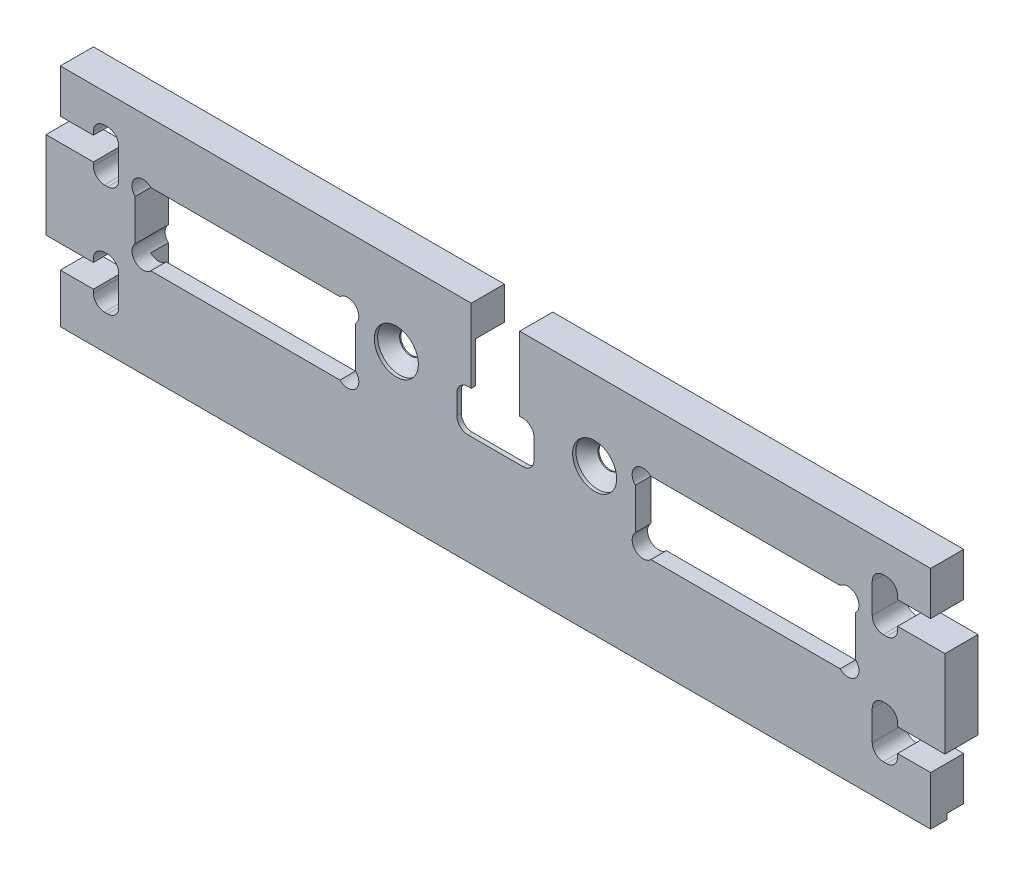
SolidWorks part; units mm, degrees
ref_plane "Front Plane" through (0, 0, 0) normal (0, 0, 1) x (1, 0, 0)
ref_plane "Top Plane" through (0, 0, 0) normal (0, 1, 0) x (1, 0, 0)
ref_plane "Right Plane" through (0, 0, 0) normal (1, 0, 0) x (0, 0, -1)
sketch "Sketch1" plane through (0, 0, 0) normal (0, 0, 1) x (1, 0, 0)
  line L0 (-39.5, 0) -> (39.5, 0) construction
  line L1 (-39.5, 10) -> (39.5, 10)
  line L2 (-39.5, 10) -> (-39.5, -10)
  line L3 (-39.5, -10) -> (39.5, -10)
  line L4 (39.5, 10) -> (39.5, -10)
  line L5 (-39.5, 10) -> (39.5, -10) construction
  line L6 (-39.5, -10) -> (39.5, 10) construction
  line L7 (0, 10) -> (0, -10) construction
  line L9 (-40.8, -3.95) -> (-39.5, -3.95)
  line L10 (-40.8, -3.95) -> (-40.8, 3.95)
  line L11 (-40.8, 3.95) -> (-39.5, 3.95)
  line L12 (-39.5, -3.95) -> (-39.5, 3.95)
  line L13 (-40.8, -3.95) -> (-39.5, 3.95) construction
  line L14 (-40.8, 3.95) -> (-39.5, -3.95) construction
  line L16 (40.8, 3.95) -> (39.5, 3.95)
  line L17 (40.8, -3.95) -> (40.8, 3.95)
  line L18 (40.8, -3.95) -> (39.5, -3.95)
  line L19 (-39.5, 5) -> (39.5, 5) construction
  line L20 (-35.35, 7.35) -> (-35.35, 2.65) construction
  line L21 (-36.5, 3.95) -> (-39.5, 3.95)
  line L22 (-36.5, 3.95) -> (-36.5, 6.05)
  line L23 (-36.5, 6.05) -> (-39.5, 6.05)
  line L24 (-39.5, 3.95) -> (-39.5, 6.05)
  line L25 (-36.5, 3.95) -> (-39.5, 6.05) construction
  line L26 (-36.5, 6.05) -> (-39.5, 3.95) construction
  line L27 (-34.2, 7.35) -> (-36.5, 7.35)
  line L28 (-34.2, 7.35) -> (-34.2, 2.65)
  line L29 (-34.2, 2.65) -> (-36.5, 2.65)
  line L30 (-36.5, 7.35) -> (-36.5, 2.65)
  line L31 (-34.2, 7.35) -> (-36.5, 2.65) construction
  line L32 (-34.2, 2.65) -> (-36.5, 7.35) construction
  line L33 (-34.2, -7.35) -> (-36.5, -7.35)
  line L34 (-34.2, -7.35) -> (-34.2, -2.65)
  line L35 (-34.2, -2.65) -> (-36.5, -2.65)
  line L36 (-36.5, -7.35) -> (-36.5, -2.65)
  line L37 (-36.5, -3.95) -> (-39.5, -3.95)
  line L38 (-36.5, -6.05) -> (-39.5, -6.05)
  line L39 (36.5, 3.95) -> (39.5, 3.95)
  line L40 (36.5, 6.05) -> (39.5, 6.05)
  line L41 (36.5, 7.35) -> (36.5, 2.65)
  line L42 (34.2, 7.35) -> (36.5, 7.35)
  line L43 (34.2, 7.35) -> (34.2, 2.65)
  line L44 (34.2, 2.65) -> (36.5, 2.65)
  line L45 (34.2, -2.65) -> (36.5, -2.65)
  line L46 (34.2, -7.35) -> (34.2, -2.65)
  line L47 (34.2, -7.35) -> (36.5, -7.35)
  line L48 (36.5, -7.35) -> (36.5, -2.65)
  line L49 (36.5, -6.05) -> (39.5, -6.05)
  line L50 (36.5, -3.95) -> (39.5, -3.95)
  point P0 (0, 0)
  point P10 (-40.15, 0)
  point P15 (-38, 5)
  point P35 (-35.35, 5)
  dimension "D1" = 79
  dimension "D2" = 20
  dimension "D4" = 1.3
  dimension "D7" = 5
  dimension "D8" = 2.1
  dimension "D9" = 3
  dimension "D10" = 2.3
  dimension "D11" = 4.7
extrude "Base shape" add sketch "Sketch1" along normal blind 3 contours L4 L1 L2 L3 | L9 L2 L11 L10 | L16 L4 L18 L17 region at (0, 0, 0) region at (-40.15, 0, 0) region at (40.15, 0, 0)
sketch "Sketch4" plane through (0, -10, 0) normal (0, -1, 0) x (1, 0, 0)
  line L0 (39.5, 3) -> (39.5, 0) construction
  line L1 (-39.5, 3) -> (39.5, 3)
  line L2 (-39.5, 3) -> (-39.5, 1.5)
  line L3 (-39.5, 1.5) -> (39.5, 1.5)
  line L4 (39.5, 3) -> (39.5, 1.5)
extrude "Floor lip" add sketch "Sketch4" along normal blind 0.5
sketch "Sketch6" plane through (0, 0, 0) normal (0, 0, -1) x (-1, 0, 0)
  line L0 (0, 0) -> (0, -10) construction
  line L1 (39.5, -10) -> (-39.5, -10) construction
  line L2 (-4, -10) -> (4, -10) construction
  line L3 (39.5, -10) -> (-39.5, -10) construction
  line L4 (-4, -9) -> (4, -9)
  line L5 (-4, -11) -> (4, -11)
  arc A0 (-4, -9) -> (-4, -11) centre (-4, -10) ccw
  arc A1 (4, -11) -> (4, -9) centre (4, -10) ccw
  point P9 (0, -10)
  dimension "D1" = 2
  dimension "D2" = 8
extrude "Nail cutout" cut sketch "Sketch6" against normal up to surface (1.5 mm away) up to face at (0, -10.25, 1.5)
sketch "Sketch3" plane through (-40.8, 0, 0) normal (-1, 0, 0) x (0, 0, 1)
  line L0 (0, 6.05) -> (3, 3.95) construction
  line L1 (0, 6.05) -> (3, 6.05)
  line L2 (0, 6.05) -> (0, 3.95)
  line L3 (0, 3.95) -> (3, 3.95)
  line L4 (3, 6.05) -> (3, 3.95)
  line L5 (0, -3.95) -> (3, -6.05) construction
  line L6 (0, -3.95) -> (3, -3.95)
  line L7 (0, -3.95) -> (0, -6.05)
  line L8 (0, -6.05) -> (3, -6.05)
  line L9 (3, -3.95) -> (3, -6.05)
  point P6 (1.5, 5)
  point P13 (1.5, -5)
ref_axis "Tap axis top" through (-53.7846, 5, 1.5) along (1, 0, 0)
ref_axis "Tap axis bottom" through (-54.2844, -5, 1.5) along (1, 0, 0)
fillet "Mill fillets" radius 1 16 edges at (36.5, -7.35, 1.5) (36.5, 2.65, 1.5) (34.2, 2.65, 1.5) (34.2, -7.35, 1.5) (36.5, -2.65, 1.5) (36.5, 7.35, 1.5) (34.2, -2.65, 1.5) (34.2, 7.35, 1.5) (-36.5, -2.65, 1.5) (-34.2, -2.65, 1.5) (-34.2, -7.35, 1.5) (-36.5, -7.35, 1.5) (-36.5, 2.65, 1.5) (-34.2, 2.65, 1.5) (-34.2, 7.35, 1.5) (-36.5, 7.35, 1.5)
sketch "Sketch8" [suppressed] plane through (0, 0, 3) normal (0, 0, 1) x (1, 0, 0)
  line L0 (-40.8, 0) -> (40.8, 0) construction
  line L1 (-40.8, -3.95) -> (-40.8, 3.95) construction
  line L2 (40.8, -3.95) -> (40.8, 3.95) construction
  line L4 (-24.5, 5.15) -> (24.5, 5.15)
  line L5 (-25.5, 4.15) -> (-25.5, -4.15)
  line L6 (-24.5, -5.15) -> (24.5, -5.15)
  line L7 (25.5, 4.15) -> (25.5, -4.15)
  line L8 (-25.5, 5.15) -> (25.5, -5.15) construction
  line L9 (-25.5, -5.15) -> (25.5, 5.15) construction
  arc A0 (24.5, -5.15) -> (25.5, -4.15) centre (24.5, -4.15) ccw
  arc A1 (24.5, 5.15) -> (25.5, 4.15) centre (24.5, 4.15) cw
  arc A2 (-25.5, -4.15) -> (-24.5, -5.15) centre (-24.5, -4.15) ccw
  arc A3 (-24.5, 5.15) -> (-25.5, 4.15) centre (-24.5, 4.15) ccw
  point P6 (0, 0)
  dimension "D3" = 1
  dimension "D1" = 51
  dimension "D2" = 10.3
extrude "Led strip pocket" [suppressed] cut sketch "Sketch8" against normal offset from surface (2.5 mm away) 0.5 up to face at (0, -0.6712, 0)
sketch "Sketch9" [suppressed] plane through (0, 0, 0.5) normal (0, 0, 1) x (1, 0, 0)
  line L0 (-19.5, 5.15) -> (-19.5, -5.15)
  line L1 (0, 5.15) -> (0, -5.15) construction
  line L2 (19.5, 5.15) -> (19.5, -5.15)
  line L3 (-25.5, -2.978) -> (25.5, -2.978) construction
  line L4 (25.5, -4.15) -> (25.5, 4.15)
  line L5 (24.5, 5.15) -> (-24.5, 5.15)
  line L6 (-25.5, 4.15) -> (-25.5, -4.15)
  line L7 (-24.5, -5.15) -> (24.5, -5.15)
  line L8 (25.5, -4.15) -> (25.5, 4.15)
  line L9 (24.5, 5.15) -> (-24.5, 5.15)
  line L10 (-25.5, 4.15) -> (-25.5, -4.15)
  line L11 (-24.5, -5.15) -> (24.5, -5.15)
  circle A0 centre (-12.7, -2.978) radius 1
  circle A1 centre (12.7, -2.978) radius 1
  arc A4 (24.5, -5.15) -> (25.5, -4.15) centre (24.5, -4.15) ccw
  arc A5 (25.5, 4.15) -> (24.5, 5.15) centre (24.5, 4.15) ccw
  arc A6 (-24.5, 5.15) -> (-25.5, 4.15) centre (-24.5, 4.15) ccw
  arc A7 (-25.5, -4.15) -> (-24.5, -5.15) centre (-24.5, -4.15) ccw
  arc A8 (24.5, -5.15) -> (25.5, -4.15) centre (24.5, -4.15) ccw
  arc A9 (25.5, 4.15) -> (24.5, 5.15) centre (24.5, 4.15) ccw
  arc A10 (-24.5, 5.15) -> (-25.5, 4.15) centre (-24.5, 4.15) ccw
  arc A11 (-25.5, -4.15) -> (-24.5, -5.15) centre (-24.5, -4.15) ccw
  arc M13 (24.5, -5.15) -> (25.5, -4.15) centre (24.5, -4.15) ccw
  line M14 (25.5, -4.15) -> (25.5, 4.15)
  arc M15 (25.5, 4.15) -> (24.5, 5.15) centre (24.5, 4.15) ccw
  line M16 (24.5, 5.15) -> (-24.5, 5.15)
  arc M17 (-24.5, 5.15) -> (-25.5, 4.15) centre (-24.5, 4.15) ccw
  line M18 (-25.5, 4.15) -> (-25.5, -4.15)
  arc M19 (-25.5, -4.15) -> (-24.5, -5.15) centre (-24.5, -4.15) ccw
  line M20 (-24.5, -5.15) -> (24.5, -5.15)
  dimension "D4" = 2
  dimension "D2" = 6
  dimension "D3" = 8.128
  dimension "D5" = 25.4
  dimension "D1" = 0
extrude "Led strip cuts" [suppressed] cut sketch "Sketch9" against normal up to next contours L0 M16 M17 M18 M19 M20 | L2 M16 M20 M13 M14 M15 | A0 | A1
fillet "Led strip cut fillets" [suppressed] radius 1
sketch "Sketch13" plane through (0, 0, 0) normal (0, 0, -1) x (-1, 0, 0)
  line L0 (0, 15.8648) -> (0, -21.9195) construction
  line L2 (-4.2, -6.3) -> (4.2, -6.3)
  line L3 (-5.2, -5.3) -> (-5.2, 6)
  line L4 (-4.2, 7) -> (4.2, 7)
  line L5 (5.2, -5.3) -> (5.2, 6)
  line L6 (-5.2, -6.3) -> (5.2, 7) construction
  line L7 (-5.2, 7) -> (5.2, -6.3) construction
  line L10 (39.5, 10) -> (-39.5, 10) construction
  arc A0 (-4.2, -6.3) -> (-5.2, -5.3) centre (-4.2, -5.3) cw
  arc A1 (4.2, -6.3) -> (5.2, -5.3) centre (4.2, -5.3) ccw
  arc A4 (5.2, 6) -> (4.2, 7) centre (4.2, 6) ccw
  arc A5 (-5.2, 6) -> (-4.2, 7) centre (-4.2, 6) cw
  point P1 (0, 0.35)
  dimension "D4" = 1
  dimension "D5" = 1
  dimension "D1" = 10.4
  dimension "D2" = 13.3
  dimension "D3" = 3
extrude "Bumper mount inner cut" cut sketch "Sketch13" against normal offset from surface (2.6 mm away) 0.4 up to face at (0, -0.0192, 3)
sketch "Sketch14" plane through (0, 0, 0) normal (0, 0, -1) x (-1, 0, 0)
  line L1 (0, 12.9528) -> (0, -14.0841) construction
  line L2 (4.2, 7) -> (-4.2, 7) construction
  line L3 (-4.2, -6.3) -> (4.2, -6.3) construction
  line L4 (-11.7, 7) -> (11.7, 7)
  line L5 (-12.7, 6) -> (-12.7, -5.3)
  line L6 (-11.7, -6.3) -> (11.7, -6.3)
  line L7 (12.7, 6) -> (12.7, -5.3)
  line L8 (-12.7, 7) -> (12.7, -6.3) construction
  line L9 (-12.7, -6.3) -> (12.7, 7) construction
  arc A1 (11.7, -6.3) -> (12.7, -5.3) centre (11.7, -5.3) ccw
  arc A2 (-12.7, -5.3) -> (-11.7, -6.3) centre (-11.7, -5.3) ccw
  arc A3 (11.7, 7) -> (12.7, 6) centre (11.7, 6) cw
  arc A4 (-12.7, 6) -> (-11.7, 7) centre (-11.7, 6) cw
  point P6 (0, 0.35)
  dimension "D2" = 1
  dimension "D3" = 1
  dimension "D1" = 25.4
extrude "Bumper mount outer cut" cut sketch "Sketch14" against normal blind 1.6
sketch "Sketch15" plane through (0, 0, 1.6) normal (0, 0, -1) x (-1, 0, 0)
  line L0 (-12.7, 2.8) -> (12.7, 2.8) construction
  line L3 (0, 16.4744) -> (0, -20.0474) construction
  line L7 (-12.7, 6) -> (-12.7, -5.3) construction
  line L8 (12.7, -5.3) -> (12.7, 6) construction
  line L11 (-4.2, 7) -> (-11.7, 7) construction
  circle A0 centre (-9, 2.8) radius 1
  circle A1 centre (9, 2.8) radius 1
  dimension "D1" = 18
  dimension "D2" = 2
  dimension "D3" = 4.2
extrude "Bumper mount screw holes" cut sketch "Sketch15" against normal up to next
sketch "Sketch16" plane through (0, 0, 2.6) normal (0, 0, -1) x (-1, 0, 0)
  line L0 (-5.2, 1.4) -> (5.2, 1.4) construction
  line L3 (0, 7) -> (0, -4.2) construction
  line L4 (-2.5, 3.3) -> (2.5, 3.3)
  line L5 (-3.5, 2.3) -> (-3.5, 0.5)
  line L6 (-2.5, -0.5) -> (2.5, -0.5)
  line L7 (3.5, 2.3) -> (3.5, 0.5)
  line L8 (-3.5, 3.3) -> (3.5, -0.5) construction
  line L9 (-3.5, -0.5) -> (3.5, 3.3) construction
  line L11 (-5.2, 6) -> (-5.2, -5.3) construction
  line L13 (4.2, 7) -> (-4.2, 7) construction
  arc A0 (2.5, -0.5) -> (3.5, 0.5) centre (2.5, 0.5) ccw
  arc A1 (-3.5, 0.5) -> (-2.5, -0.5) centre (-2.5, 0.5) ccw
  arc A2 (-2.5, 3.3) -> (-3.5, 2.3) centre (-2.5, 2.3) ccw
  arc A3 (2.5, 3.3) -> (3.5, 2.3) centre (2.5, 2.3) cw
  point P6 (0, 1.4)
  dimension "D3" = 1
  dimension "D1" = 7
  dimension "D2" = 3.8
  dimension "D4" = 11.2
extrude "Bumper body cut" cut sketch "Sketch16" against normal up to next
hole_wizard "Bumper screw countersunks" positions "Sketch17" profile "Sketch18" countersink size "M2" standard "ANSI Metric" end condition through all
sketch "Sketch17" plane through (0, 0, 3) normal (0, 0, 1) x (1, 0, 0)
  point P0 (9, 2.8)
  point P3 (-9, 2.8)
sketch "Sketch18" plane through (9, 2.8, 3) normal (1, 0, 0) x (0, -1, 0)
  line L0 (0, 0) -> (0, 3)
  line L1 (0, 3) -> (1, 3)
  line L2 (1, 3) -> (1, 1.3)
  line L3 (1, 1.3) -> (2, 0.3)
  line L4 (2, 0.3) -> (2, 0)
  line L6 (2, 0) -> (0, 0)
  line L7 (-1, 1.3) -> (-2, 0.3) construction
  line L11 (0, -6.35) -> (0, 107.95) construction
  dimension "Thru Hole Dia." = 2
  dimension "Thru Hole Depth" = 3
  dimension "C'Sink Dia." = 4
  dimension "C'Sink Angle" = 90
  dimension "Head Clearance" = 0.3
sketch "Sketch19" plane through (0, 0, 0) normal (0, 0, -1) x (-1, 0, 0)
  line L0 (0, 15.6498) -> (0, -12.9575) construction
  line L1 (39.5, 10) -> (-39.5, 10) construction
  line L2 (-2.2, 3.3) -> (2.2, 3.3)
  line L3 (-2.2, 3.3) -> (-2.2, 10)
  line L4 (-2.2, 10) -> (2.2, 10)
  line L5 (2.2, 3.3) -> (2.2, 10)
  line L6 (-2.2, 3.3) -> (2.2, 10) construction
  line L7 (-2.2, 10) -> (2.2, 3.3) construction
  line L8 (2.5, 3.3) -> (-2.5, 3.3) construction
  point P1 (0, 6.65)
  dimension "D1" = 4.4
extrude "Bumper insertion cut" cut sketch "Sketch19" against normal up to next
sketch "Sketch20" plane through (0, 0, 0) normal (0, 0, -1) x (-1, 0, 0)
  line L0 (-12.7, 6) -> (-12.7, -5.3) construction
  line L1 (-12.7, 4.55) -> (-32.7, 4.55)
  line L2 (-12.7, 4.55) -> (-12.7, -2)
  line L3 (-12.7, -2) -> (-32.7, -2)
  line L4 (-32.7, 4.55) -> (-32.7, -2)
  line L5 (-2.2, 10) -> (-39.5, 10) construction
  line L6 (-12.7, 4.55) -> (-19.25, -2) construction
  line L7 (-22.7, 4.55) -> (-22.7, -2) construction
  line L8 (-32.7, 1.275) -> (-12.7, 1.275) construction
  line L9 (0, 16.176) -> (0, -15.99) construction
  line L10 (12.7, 4.55) -> (12.7, -2)
  line L11 (12.7, -2) -> (32.7, -2)
  line L12 (32.7, 4.55) -> (32.7, -2)
  line L13 (12.7, 4.55) -> (32.7, 4.55)
  circle A0 centre (-13.4071, 3.8429) radius 1
  circle A1 centre (-31.9929, 3.8429) radius 1
  circle A2 centre (-13.4071, -1.2929) radius 1
  circle A3 centre (-31.9929, -1.2929) radius 1
  circle A4 centre (13.4071, 3.8429) radius 1
  circle A5 centre (13.4071, -1.2929) radius 1
  circle A6 centre (31.9929, -1.2929) radius 1
  circle A7 centre (31.9929, 3.8429) radius 1
  dimension "D5" = 2
  dimension "D1" = 20
  dimension "D2" = 5.45
  dimension "D3" = 6.55
  dimension "D4" = 45
extrude "Bumper switches cut" cut sketch "Sketch20" against normal up to next contours L1 L4 L3 L2 | A1 | A3 | A0 | A2 | L13 L12 L11 L10 | A4 | A5 | A6 | A7
sketch "Sketch21" plane through (0, 0, 0) normal (0, 0, -1) x (-1, 0, 0)
  line L0 (-14.1142, -2) -> (-31.2858, -2) construction
  line L1 (-32.7, -2) -> (-12.7, -2)
  line L2 (-32.7, -2) -> (-32.7, -6.3)
  line L3 (-32.7, -6.3) -> (-12.7, -6.3)
  line L4 (-12.7, -2) -> (-12.7, -6.3)
  line L5 (-12.7, -2) -> (-12.7, -5.3) construction
  line L6 (-11.7, -6.3) -> (-4.2, -6.3) construction
  line L7 (-32.7, 3.1358) -> (-32.7, -0.5858) construction
  line L8 (-12.7, -6.3) -> (-11.7, -6.3)
  line L9 (-32.7, -6.3) -> (-28.4, -2) construction
  line L10 (0, 14.2019) -> (0, -15.3745) construction
  line L11 (12.7, -6.3) -> (11.7, -6.3)
  line L12 (12.7, -2) -> (12.7, -6.3)
  line L13 (32.7, -2) -> (12.7, -2)
  line L14 (32.7, -2) -> (32.7, -6.3)
  line L15 (32.7, -6.3) -> (12.7, -6.3)
  arc A0 (-12.7, -5.3) -> (-11.7, -6.3) centre (-11.7, -5.3) ccw construction
  arc A1 (-12.7, -5.3) -> (-11.7, -6.3) centre (-11.7, -5.3) ccw
  circle A2 centre (-31.9929, -5.5929) radius 1
  arc A3 (-32.7, -0.5858) -> (-31.2858, -2) centre (-31.9929, -1.2929) ccw construction
  circle A4 centre (31.9929, -5.5929) radius 1
  arc A5 (12.7, -5.3) -> (11.7, -6.3) centre (11.7, -5.3) cw
  dimension "D1" = 45
extrude "Bumper switch mounts cut" cut sketch "Sketch21" against normal up to surface (1.6 mm away) contours A1 L4 L8 | L12 A5 L11 | L4 L1 L2 L3 | A2 | L12 L13 L14 L15 | A4 region at (12.4766, -6.0766, 0) region at (-12.4766, -6.0766, 0) up to face at (-8, 2.8, 1.6)
sketch "Outer coordinate system sketch" plane through (0, 0, 3) normal (0, 0, 1) x (1, 0, 0)
  line L0 (-35.35, 7.35) -> (-35.35, 2.65) construction
  line L1 (-35.2, 7.35) -> (-35.5, 7.35) construction
  line L2 (-40.8, 3.95) -> (-40.8, 10) construction
  line L3 (-40.8, 10) -> (-39.5, 10) construction
  line L4 (-35.2, 2.65) -> (-35.5, 2.65) construction
  line L5 (0, 15.526) -> (0, -17.3739) construction
  line L6 (-51.2617, 0) -> (56.0692, 0) construction
  circle A0 centre (-35.35, 6.35) radius 1
  point P16 (-35.35, 6.35)
  point P20 (0, 0)
  point P22 (35.35, 6.35)
  point P23 (0, 0)
  point P24 (-35.35, -6.35)
  point P25 (35.35, -6.35)
  dimension "D1" = 2
sketch "Inner coordinate system sketch" plane through (0, 0, 0) normal (0, 0, 1) x (1, 0, 0)
  line L0 (-40.8, -3.95) -> (-40.8, -10) construction
  line L1 (-40.8, -10) -> (-39.5, -10) construction
  line L3 (0, 19.9465) -> (0, -19.5427) construction
  line L4 (53.9633, 0) -> (-51.6097, 0) construction
  point P1 (0, 0)
  point P4 (0, 0)
  point P5 (0, 0)
  point P6 (0, 0)
  point P9 (0, 0)
  point P11 (0, 0)
  point P15 (-39.5, -10)
sketch "Deep inner pocket mill sketch" plane through (0, 0, 2.6) normal (0, 0, -1) x (-1, 0, 0)
  line L0 (-4.2, 7) -> (4.2, 7)
  line L12 (4.2, 7) -> (2.2, 7)
  line L13 (2.2, 7) -> (2.2, 3.3)
  line L14 (2.2, 3.3) -> (2.5, 3.3)
  line L15 (3.5, 2.3) -> (3.5, 0.5)
  line L16 (2.5, -0.5) -> (-2.5, -0.5)
  line L17 (-3.5, 0.5) -> (-3.5, 2.3)
  line L18 (-2.5, 3.3) -> (-2.2, 3.3)
  line L19 (-2.2, 3.3) -> (-2.2, 7)
  line L20 (-2.2, 7) -> (-4.2, 7)
  line L21 (-5.2, 6) -> (-5.2, -5.3)
  line L22 (-4.2, -6.3) -> (4.2, -6.3)
  line L23 (5.2, -5.3) -> (5.2, 6)
  line L33 (-5.2, 6) -> (-5.2, -5.3)
  line L34 (-4.2, -6.3) -> (4.2, -6.3)
  line L35 (5.2, -5.3) -> (5.2, 6)
  arc A8 (3.5, 2.3) -> (2.5, 3.3) centre (2.5, 2.3) ccw
  arc A9 (2.5, -0.5) -> (3.5, 0.5) centre (2.5, 0.5) ccw
  arc A10 (-3.5, 0.5) -> (-2.5, -0.5) centre (-2.5, 0.5) ccw
  arc A11 (-2.5, 3.3) -> (-3.5, 2.3) centre (-2.5, 2.3) ccw
  arc A12 (-4.2, 7) -> (-5.2, 6) centre (-4.2, 6) ccw
  arc A13 (-5.2, -5.3) -> (-4.2, -6.3) centre (-4.2, -5.3) ccw
  arc A14 (4.2, -6.3) -> (5.2, -5.3) centre (4.2, -5.3) ccw
  arc A15 (5.2, 6) -> (4.2, 7) centre (4.2, 6) ccw
  arc A20 (-4.2, 7) -> (-5.2, 6) centre (-4.2, 6) ccw
  arc A21 (-5.2, -5.3) -> (-4.2, -6.3) centre (-4.2, -5.3) ccw
  arc A22 (4.2, -6.3) -> (5.2, -5.3) centre (4.2, -5.3) ccw
  arc A23 (5.2, 6) -> (4.2, 7) centre (4.2, 6) ccw
  dimension "D1" = 0
sketch "Shallow inner pocket mill sketch" plane through (0, 0, 1.6) normal (0, 0, -1) x (-1, 0, 0)
  line L2 (12.7, 4.55) -> (12.7, 6) construction
  line L7 (-12.7, 6) -> (-12.7, 4.55) construction
  line L16 (12.7, 4.55) -> (12.7, 6)
  line L21 (-12.7, 6) -> (-12.7, 4.55)
  line L42 (-32.7, -1) -> (-13.7, -1)
  line L43 (-12.7, 3.1358) -> (-12.7, -0.5858) construction
  line L47 (0, 16.1275) -> (0, -14.7685) construction
  line L53 (-31.2858, -6.3) -> (31.2858, -6.3)
  line L54 (-11.7, 7) -> (11.7, 7)
  line L55 (-12.7, 4.55) -> (-13.7, 4.55)
  line L56 (-13.7, 4.55) -> (-13.7, -1)
  line L58 (-22.7, -2) -> (-22.7, -1) construction
  line L59 (-31.2858, -2) -> (-14.1142, -2) construction
  line L60 (-12.7, 1.275) -> (-13.7, 1.275) construction
  line L61 (-32.7, -1) -> (-32.7, -4.8858)
  line L62 (12.7, 4.55) -> (13.7, 4.55)
  line L63 (13.7, 4.55) -> (13.7, -1)
  line L64 (32.7, -1) -> (13.7, -1)
  line L65 (32.7, -1) -> (32.7, -4.8858)
  arc A2 (12.7, 6) -> (11.7, 7) centre (11.7, 6) ccw construction
  arc A5 (31.2858, -6.3) -> (32.7, -4.8858) centre (31.9929, -5.5929) ccw construction
  arc A10 (-32.7, -4.8858) -> (-31.2858, -6.3) centre (-31.9929, -5.5929) ccw construction
  arc A13 (-11.7, 7) -> (-12.7, 6) centre (-11.7, 6) ccw construction
  arc A16 (12.7, 6) -> (11.7, 7) centre (11.7, 6) ccw
  arc A19 (31.2858, -6.3) -> (32.7, -4.8858) centre (31.9929, -5.5929) ccw
  arc A24 (-32.7, -4.8858) -> (-31.2858, -6.3) centre (-31.9929, -5.5929) ccw
  arc A27 (-11.7, 7) -> (-12.7, 6) centre (-11.7, 6) ccw
  dimension "D1" = 1
